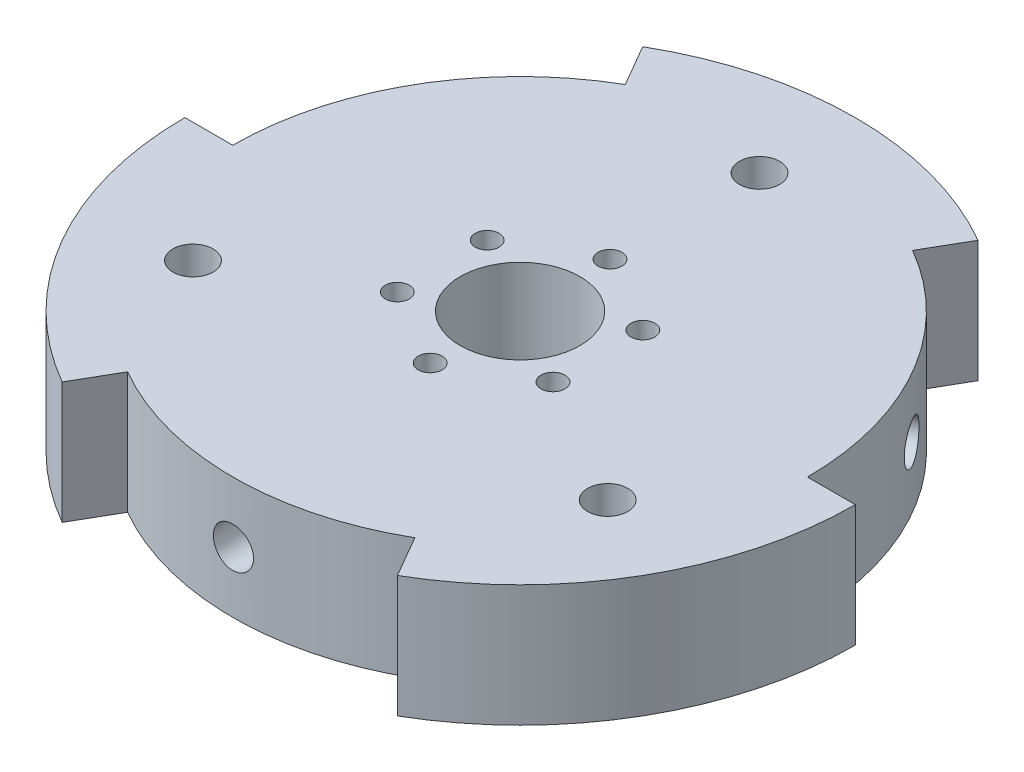
SolidWorks part; units mm, degrees
ref_plane "Front Plane" through (0, 0, 0) normal (0, 0, 1) x (1, 0, 0)
ref_plane "Top Plane" through (0, 0, 0) normal (0, 1, 0) x (1, 0, 0)
ref_plane "Right Plane" through (0, 0, 0) normal (1, 0, 0) x (0, 0, -1)
sketch "Baseplate Sketch" plane through (0, 0, 0) normal (0, 1, 0) x (1, 0, 0)
  line L0 (0, 0) -> (0, 61.4504) construction
  line L1 (-17.5, 30.3109) -> (-15, 25.9808)
  line L2 (17.5, 30.3109) -> (15, 25.9808)
  line L3 (-17.5, 30.3109) -> (-21.8301, 27.8109) construction
  line L4 (17.5, 30.3109) -> (13.1699, 32.8109) construction
  line L5 (17.5, -30.3109) -> (15, -25.9808)
  line L6 (35, 0) -> (30, 0)
  line L7 (-35, 0) -> (-30, 0)
  line L8 (-17.5, -30.3109) -> (-15, -25.9808)
  circle A0 centre (0, 0) radius 30
  circle A1 centre (0, 0) radius 6.25
  arc A2 (-17.5, 30.3109) -> (17.5, 30.3109) centre (0, 0) cw
  arc A3 (35, 0) -> (17.5, -30.3109) centre (0, 0) cw
  arc A4 (-17.5, -30.3109) -> (-35, 0) centre (0, 0) cw
  circle A5 centre (0, 25) radius 2.1
  circle A6 centre (21.6506, -12.5) radius 2.1
  circle A7 centre (-21.6506, -12.5) radius 2.1
  point P15 (0, 35)
  point P25 (0, 0)
  point P31 (0, 0)
  dimension "D1" = 60
  dimension "D2" = 12.5
  dimension "D3" = 35
  dimension "D4" = 90
  dimension "D5" = 5
  dimension "D12" = 4.2
  dimension "D6" = 5
  dimension "D7" = 90
  dimension "D8" = 60
  dimension "D9" = 5
  dimension "D10" = 5
  dimension "D14" = 25
  dimension "D11" = 3
  dimension "D13" = 3
extrude "Boss-Extrude1" add sketch "Baseplate Sketch" along normal blind 12.7 contours A4 L8 A0 L7 | A3 L6 A0 L5 | A2 L1 A0 L2 | A0 | A1 | A6 | A7 | A5 region at (0, 0, -31.0964) region at (-26.9303, 0, 15.5482) region at (26.9303, 0, 15.5482)
ref_plane "Plane1" through (0, 0, 40) normal (0, 0, 1) x (1, 0, 0)
sketch "Sketch2" plane through (0, 0, 40) normal (0, 0, 1) x (1, 0, 0)
  line L0 (0, 12.7) -> (0, 0) construction
  line L4 (15, 12.7) -> (-15, 12.7)
  line L5 (-15, 12.7) -> (-15, 0)
  line L6 (-15, 0) -> (15, 0)
  line L7 (15, 0) -> (15, 12.7)
  line L8 (15, 12.7) -> (-15, 12.7) construction
  line L9 (-15, 12.7) -> (-15, 0) construction
  line L10 (-15, 0) -> (15, 0) construction
  line L11 (15, 0) -> (15, 12.7) construction
  circle A0 centre (0, 6.35) radius 2.1
  dimension "D1" = 0
  dimension "D2" = 4.2
extrude "Cut-Extrude1" cut sketch "Sketch2" against normal blind 25
pattern_circular "CirPattern1" count 3 over 360 about axis through (0, 12.7, 0) along (0, 1, 0) of "Cut-Extrude1"
sketch "Sketch3" plane through (0, 12.7, 0) normal (0, 1, 0) x (1, 0, 0)
  circle A2 centre (-8.1276, -4.6925) radius 1.25
  circle A5 centre (0, -9.385) radius 1.25
  circle A6 centre (-8.1276, 4.6925) radius 1.25
  circle A7 centre (0, 9.385) radius 1.25
  circle A8 centre (8.1276, 4.6925) radius 1.25
  circle A9 centre (8.1276, -4.6925) radius 1.25
  point P14 (0, 0)
  dimension "D1" = 2.5
  dimension "D2" = 9.385
  dimension "D3" = 9.385
extrude "Cut-Extrude2" cut sketch "Sketch3" against normal up to surface (12.7 mm away) contours A5 | A2 | A6 | A7 | A8 | A9 region at (-8.1276, 12.7, 4.6925) region at (0, 12.7, 9.385) region at (-8.1276, 12.7, -4.6925) region at (0, 12.7, -9.385) region at (8.1276, 12.7, -4.6925) region at (8.1276, 12.7, 4.6925) up to face at (0, 0, 0)
